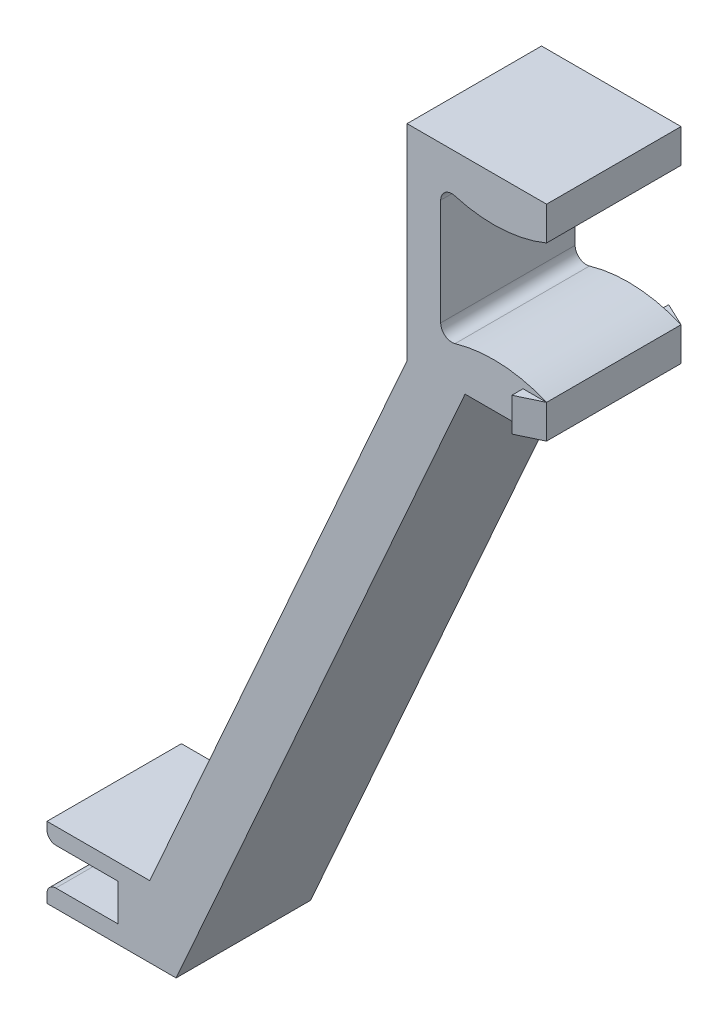
SolidWorks part; units mm, degrees
ref_plane "Front Plane" through (0, 0, 0) normal (0, 0, 1) x (1, 0, 0)
ref_plane "Top Plane" through (0, 0, 0) normal (0, 1, 0) x (1, 0, 0)
ref_plane "Right Plane" through (0, 0, 0) normal (1, 0, 0) x (0, 0, -1)
sketch "Sketch1" plane through (0, 0, 0) normal (0, 0, 1) x (1, 0, 0)
  line L2 (-159.7982, 9.1594) -> (-172.2482, 9.1594)
  line L3 (-172.2482, 9.1594) -> (-172.2482, -9.1594)
  line L7 (-169.2482, -22.8519) -> (-169.2482, 6.1594) construction
  line L12 (-169.2482, 5.1594) -> (-169.2482, 1.9844) construction
  line L13 (-142.8048, 5.1594) -> (-142.8048, -5.1594) construction
  line L15 (-156.5482, 5.1594) -> (21.2518, 5.1594) construction
  line L16 (-156.5482, -5.1594) -> (21.2518, -5.1594) construction
  line L23 (-159.7982, 6.1594) -> (-159.7982, 9.1594)
  line L28 (-164.5232, 5.2094) -> (-144.5007, 5.2094) construction
  line L29 (-156.5482, 5.1594) -> (-169.2482, 5.1594) construction
  line L30 (-169.2482, 6.1594) -> (-169.2482, 5.1594)
  line L34 (-169.2482, 5.1594) -> (-169.2482, -5.1594)
  line L35 (-172.2482, 0) -> (-169.2482, 0) construction
  line L36 (-169.2482, -6.1594) -> (-169.2482, -5.1594)
  line L37 (-159.7982, -6.1594) -> (-159.7982, -9.1594)
  line L38 (-159.7982, -9.1594) -> (-172.2482, -9.1594)
  line L39 (-159.7982, 5.1594) -> (-159.7982, 1.9844) construction
  arc A5 (-169.2482, 6.1594) -> (-159.7982, 6.1594) centre (-164.5232, 17.4347) ccw
  arc A6 (-169.2482, -6.1594) -> (-159.7982, -6.1594) centre (-164.5232, -17.4347) cw
  point P30 (-142.8048, 0)
  dimension "D4" = 3
  dimension "D3" = 3
  dimension "D1" = 0.05
  dimension "D2" = 1
extrude "MainBody" add sketch "Sketch1" along normal mid plane 12
sketch "Sketch3" plane through (0, -9.1594, 0) normal (0, -1, 0) x (1, 0, 0)
  line L0 (-159.7982, -6) -> (-161.8982, -7)
  line L1 (-161.8982, -7) -> (-161.8982, -6)
  line L2 (-172.2482, -6) -> (-159.7982, -6) construction
  line L3 (-161.8982, -6) -> (-159.7982, -6)
  line L4 (-162.8982, -12.7) -> (-162.8982, -6.35) construction
  line L5 (6.8475, 0) -> (-6.8475, 0) construction
  line L6 (-161.8982, 6) -> (-159.7982, 6)
  line L7 (-161.8982, 7) -> (-161.8982, 6)
  line L8 (-159.7982, 6) -> (-161.8982, 7)
  dimension "D1" = 1
  dimension "D2" = 1
extrude "Hook" add sketch "Sketch3" against normal up to vertex (3 mm away) up to point (-159.7982, -6.1594, -6)
fillet "Fillet2" radius 1 2 edges at (-169.2482, 6.1594, 0) (-169.2482, -6.1594, 0)
sketch "Sketch5" [suppressed] plane through (-172.2482, 0, 0) normal (-1, 0, 0) x (0, 0, 1)
  line L1 (-6, 9.1594) -> (6, 9.1594)
  line L2 (-6, 9.1594) -> (-6, -9.1594)
  line L3 (-6, -9.1594) -> (6, -9.1594)
  line L4 (6, 9.1594) -> (6, -9.1594)
extrude "Boss-Extrude1" [suppressed] add sketch "Sketch5" along normal blind 15
sketch "Sketch6" [suppressed] plane through (0, 9.1594, 0) normal (0, 1, 0) x (1, 0, 0)
  line L0 (-187.2482, -6) -> (-187.2482, 6) construction
  circle A0 centre (-182.2482, 0) radius 3.302
  dimension "D1" = 6.604
  dimension "D2" = 5
extrude "Cut-Extrude2" [suppressed] cut sketch "Sketch6" against normal through all
sketch "Sketch7" plane through (-172.2482, 0, 0) normal (-1, 0, 0) x (0, 0, 1)
  circle A0 centre (0, 0) radius 38.1
  dimension "D1" = 76.2
extrude "Boss-Extrude2" [suppressed] add sketch "Sketch7" along normal blind 5
fillet "Fillet3" [suppressed] radius 1
sketch "Sketch8" plane through (0, 0, 6) normal (0, 0, 1) x (1, 0, 0)
  line L6 (-172.2482, -0.635) -> (-173.4343, -0.635)
  line L8 (-172.2482, 0.635) -> (-173.4343, 0.635)
  line L10 (-172.2482, 0.635) -> (-173.4343, 0.635)
  line L11 (-172.2482, 0.635) -> (-172.2482, -0.635)
  line L12 (-161.8982, -9.1594) -> (-161.8982, -6.1594)
  line L13 (-161.8982, -6.1594) -> (-159.7982, -6.1594)
  line L14 (-169.2482, -4.7448) -> (-169.2482, 4.7448)
  line L15 (-159.7982, 6.1594) -> (-159.7982, 9.1594)
  line L16 (-159.7982, 9.1594) -> (-172.2482, 9.1594)
  line L17 (-172.2482, 9.1594) -> (-172.2482, -9.1594)
  line L18 (-172.2482, -9.1594) -> (-161.8982, -9.1594)
  line L19 (-161.8982, -9.1594) -> (-161.8982, -6.1594)
  line L20 (-161.8982, -6.1594) -> (-159.7982, -6.1594)
  line L21 (-169.2482, -4.7448) -> (-169.2482, 4.7448)
  line L22 (-159.7982, 6.1594) -> (-159.7982, 9.1594)
  line L23 (-159.7982, 9.1594) -> (-172.2482, 9.1594)
  line L24 (-172.2482, 9.1594) -> (-172.2482, -9.1594)
  line L25 (-172.2482, -9.1594) -> (-161.8982, -9.1594)
  line L26 (-172.2482, -0.635) -> (-173.4343, -0.635)
  arc A0 (-173.4343, 0.635) -> (-173.4343, -0.635) centre (-174.5342, 0) ccw
  arc A4 (-159.7982, -6.1594) -> (-167.9665, -5.7043) centre (-164.5232, -17.4347) ccw
  arc A5 (-169.2482, -4.7448) -> (-167.9665, -5.7043) centre (-168.2482, -4.7448) ccw
  arc A6 (-167.9665, 5.7043) -> (-169.2482, 4.7448) centre (-168.2482, 4.7448) ccw
  arc A7 (-167.9665, 5.7043) -> (-159.7982, 6.1594) centre (-164.5232, 17.4347) ccw
  arc A8 (-159.7982, -6.1594) -> (-167.9665, -5.7043) centre (-164.5232, -17.4347) ccw
  arc A9 (-169.2482, -4.7448) -> (-167.9665, -5.7043) centre (-168.2482, -4.7448) ccw
  arc A10 (-167.9665, 5.7043) -> (-169.2482, 4.7448) centre (-168.2482, 4.7448) ccw
  arc A11 (-167.9665, 5.7043) -> (-159.7982, 6.1594) centre (-164.5232, 17.4347) ccw
  point P6 (-172.2482, 0)
  line M14 (-172.2482, 9.1594) -> (-172.2482, -9.1594)
  dimension "D2" = 1.27
  dimension "D1" = 0
  dimension "D3" = 2.286
extrude "Slot" [suppressed] add sketch "Sketch8" against normal up to surface (12 mm away) contours L8 A0 L6 M14 up to face at (-165.6835, -0.5599, -6)
sketch "Sketch10" plane through (0, 0, -6) normal (0, 0, -1) x (-1, 0, 0)
  line L0 (167.0732, -9.1594) -> (172.2482, -9.1594)
  line L2 (167.0732, -9.1594) -> (192.863, -67.1864)
  line L3 (172.2482, -9.1594) -> (167.0732, -9.1594)
  line L5 (172.2482, -9.1594) -> (195.2157, -60.8364)
  line L6 (198.038, -67.1864) -> (192.863, -67.1864)
  line L7 (159.7982, -6.1594) -> (161.8982, -6.1594)
  line L8 (161.8982, -6.1594) -> (161.8982, -9.1594)
  line L9 (161.8982, -9.1594) -> (172.2482, -9.1594)
  line L10 (172.2482, -9.1594) -> (172.2482, 9.1594)
  line L11 (172.2482, 9.1594) -> (159.7982, 9.1594)
  line L12 (159.7982, 9.1594) -> (159.7982, 6.1594)
  line L13 (169.2482, 4.7448) -> (169.2482, -4.7448)
  line L14 (159.7982, -6.1594) -> (161.8982, -6.1594)
  line L15 (161.8982, -6.1594) -> (161.8982, -9.1594)
  line L16 (161.8982, -9.1594) -> (172.2482, -9.1594)
  line L17 (172.2482, -9.1594) -> (172.2482, 9.1594)
  line L18 (172.2482, 9.1594) -> (159.7982, 9.1594)
  line L19 (159.7982, 9.1594) -> (159.7982, 6.1594)
  line L20 (169.2482, 4.7448) -> (169.2482, -4.7448)
  line L21 (198.038, -67.1864) -> (204.388, -67.1864)
  line L22 (204.388, -67.1864) -> (204.388, -65.5989)
  line L23 (204.388, -60.8364) -> (195.2157, -60.8364)
  line L24 (204.388, -62.2969) -> (204.388, -60.8364)
  line L26 (204.388, -62.2969) -> (198.038, -62.2969)
  line L28 (204.388, -65.5989) -> (198.038, -65.5989)
  line L29 (198.038, -62.2969) -> (198.038, -65.5989)
  arc A4 (167.9665, -5.7043) -> (159.7982, -6.1594) centre (164.5232, -17.4347) ccw
  arc A5 (159.7982, 6.1594) -> (167.9665, 5.7043) centre (164.5232, 17.4347) ccw
  arc A6 (169.2482, 4.7448) -> (167.9665, 5.7043) centre (168.2482, 4.7448) ccw
  arc A7 (167.9665, -5.7043) -> (169.2482, -4.7448) centre (168.2482, -4.7448) ccw
  arc A8 (167.9665, -5.7043) -> (159.7982, -6.1594) centre (164.5232, -17.4347) ccw
  arc A9 (159.7982, 6.1594) -> (167.9665, 5.7043) centre (164.5232, 17.4347) ccw
  arc A10 (169.2482, 4.7448) -> (167.9665, 5.7043) centre (168.2482, 4.7448) ccw
  arc A11 (167.9665, -5.7043) -> (169.2482, -4.7448) centre (168.2482, -4.7448) ccw
  line M18 (161.8982, -9.1594) -> (172.2482, -9.1594)
  dimension "D2" = 5.175
  dimension "D3" = 63.5
  dimension "D4" = 6.35
  dimension "D5" = 6.35
  dimension "D6" = 3.302
extrude "Boss-Extrude3" add sketch "Sketch10" against normal up to surface (12 mm away) contours L6 L5 L2 M18 region at (-184.051, -40.3745, -6) up to face at (-165.6835, -0.5599, 6)
fillet "Fillet4" radius 0.7937 2 edges at (-204.388, -65.5989, 0) (-204.388, -62.2969, 0)
equation "\"HookThickness\"= 3mm"
equation "\"D3@Sketch1\"=\"HookThickness\""
equation "\"D4@Sketch1\"=\"HookThickness\""
equation "\"CylinderDiameter\"=3"
equation "\"D1@Sketch7\"=\"CylinderDiameter\""
equation "\"Mount Tolerance\" = .005in"
equation "\"D6@Sketch10\"= .125 + \"Mount Tolerance\""
